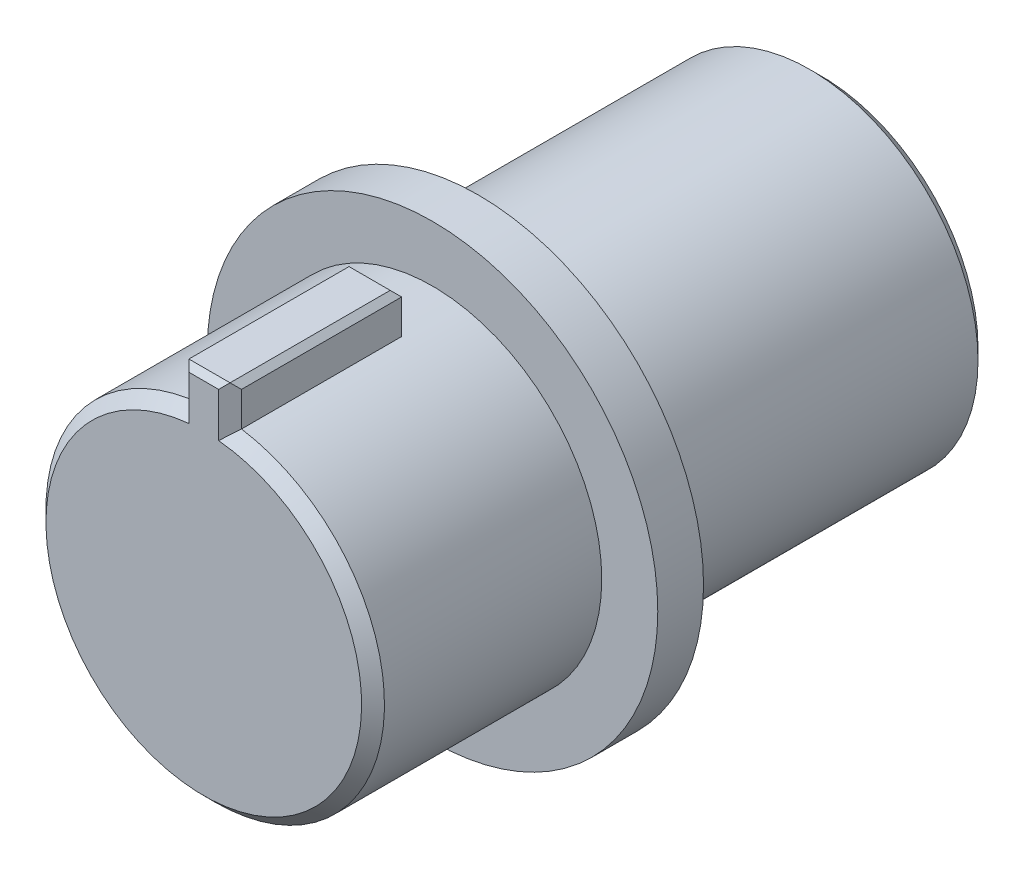
SolidWorks part; units mm, degrees
ref_plane "Front Plane" through (0, 0, 0) normal (0, 0, 1) x (1, 0, 0)
ref_plane "Top Plane" through (0, 0, 0) normal (0, 1, 0) x (1, 0, 0)
ref_plane "Right Plane" through (0, 0, 0) normal (1, 0, 0) x (0, 0, -1)
sketch "Sketch1" plane through (0, 0, 0) normal (0, 0, 1) x (1, 0, 0)
  circle A0 centre (-50, 10.3) radius 14.7
  dimension "D1" = 29.4
extrude "Boss-Extrude1" add sketch "Sketch1" against normal blind 30
sketch "Sketch2" plane through (0, 0, 0) normal (0, 0, 1) x (1, 0, 0)
  circle A2 centre (-50, 10.3) radius 19.7
  circle A3 centre (-50, 10.3) radius 19.7
  dimension "D1" = 5
extrude "Boss-Extrude2" add sketch "Sketch2" along normal blind 4
sketch "Sketch3" plane through (0, 0, 4) normal (0, 0, 1) x (1, 0, 0)
  circle A1 centre (-50, 10.3) radius 14.8
  dimension "D1" = 29.6
extrude "Boss-Extrude3" add sketch "Sketch3" along normal blind 20
sketch "Sketch5" plane through (0, 0, 24) normal (0, 0, 1) x (1, 0, 0)
  line L0 (-50, 10.3) -> (-50, 34.8565) construction
  line L1 (-52.3, 24.9202) -> (-52.3, 28.4202)
  line L2 (-52.3, 28.4202) -> (-47.7, 28.4202)
  line L3 (-47.7, 24.9202) -> (-47.7, 28.4202)
  circle A0 centre (-50, 10.3) radius 14.8 construction
  arc A1 (-47.7, 24.9202) -> (-52.3, 24.9202) centre (-50, 10.3) ccw
  point P9 (-50, 28.4202)
  dimension "D1" = 4.6
  dimension "D2" = 3.5
extrude "Boss-Extrude4" add sketch "Sketch5" against normal blind 15
chamfer "Chamfer1" distance 0.5 angle 45 4 edges at (-52.3, 28.4202, 16.5) (-50, 28.4202, 9) (-47.7, 28.4202, 16.5) (-50, 28.4202, 24)
chamfer "Chamfer2" distance 1 angle 45 4 edges at (-47.7, 26.4202, 24) (-52.3, 26.4202, 24) (-50, -4.5, 24) (-35.3, 10.3, -30)
